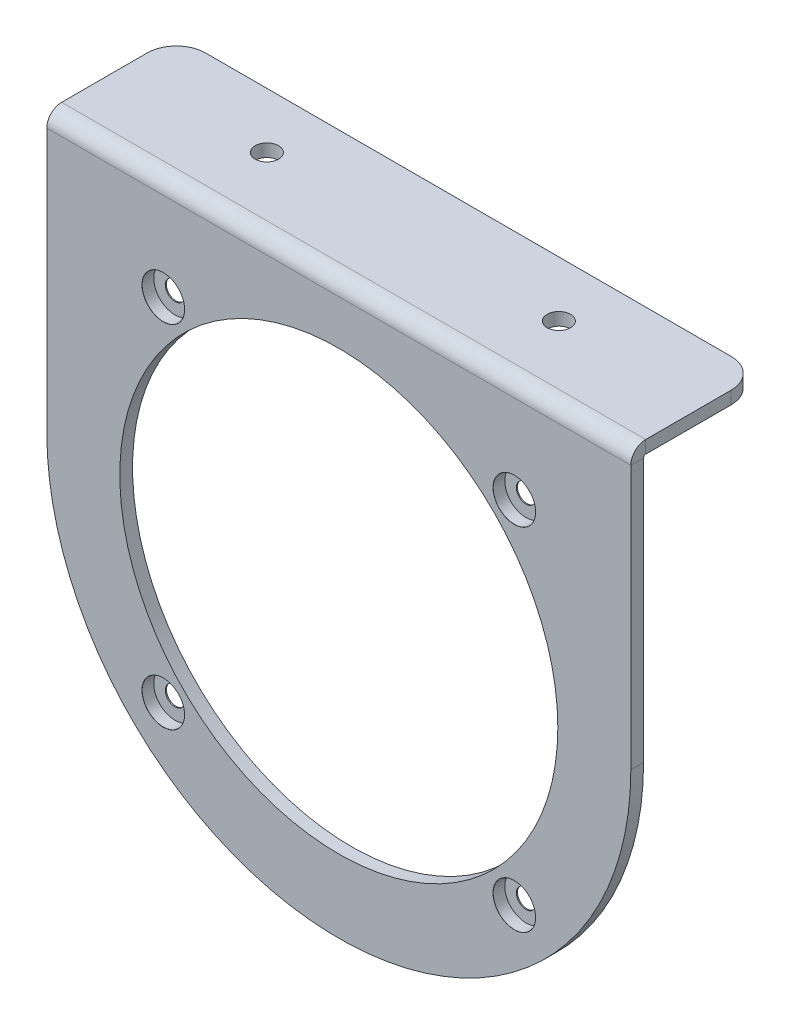
SolidWorks part; units mm, degrees
note: '?' marks a value the reader was unsure of. The reader was unsure of these and kept them because the rebuilt part matched: flange length of "Edge-Flange1"; thickness of "Edge-Flange1".
ref_plane "Front Plane" through (0, 0, 0) normal (0, 0, 1) x (1, 0, 0)
ref_plane "Top Plane" through (0, 0, 0) normal (0, 1, 0) x (1, 0, 0)
ref_plane "Right Plane" through (0, 0, 0) normal (1, 0, 0) x (0, 0, -1)
sketch "Sketch2" plane through (0, 0, 0) normal (0, 0, 1) x (1, 0, 0)
  line L0 (-100, 0) -> (-100, 95.4)
  line L1 (-100, 95.4) -> (100, 95.4)
  line L2 (100, 95.4) -> (100, 0)
  arc A0 (-100, 0) -> (100, 0) centre (0, 0) ccw
  dimension "D1" = 100
  dimension "D2" = 95.4
base flange "Base-Flange1" sketch "Sketch2" thickness 4.365 reverse thickness direction no parameters "D1"=0.7366
edge flange "Edge-Flange1" sketch "Sketch9" flange angle 90 flange length 40 flange position material inside bend radius 0.7366 thickness 4.365 relief rectangular parameters "D6"=10
sketch "Sketch9" plane through (0, 95.4, -4.365) normal (0, 1, 0) x (1, 0, 0)
  line L2 (-100, 0) -> (-100, 40)
  line L3 (-100, 40) -> (100, 40)
  line L4 (100, 40) -> (100, 0)
  line L11 (100, 0) -> (-100, 0) construction
  line L12 (100, 0) -> (-100, 0)
  dimension "D1" = 40
bend "EdgeBend1" bend radius 0.7366 bend angle 90 parameters "D5"=1
sketch "Sketch10" plane through (0, 0, 0) normal (0, 0, 1) x (1, 0, 0)
  circle A0 centre (0, 0) radius 75
  dimension "D1" = 150
extrude "Cut-Extrude1" cut sketch "Sketch10" against normal blind 10 normal cut yes
ref_axis "Axis1" through (0, 0, -4.365) along (0, 0, 1)?
fillet "Fillet1" radius 10 2 edges at (-100, 93.2175, -44.365) (100, 93.2175, -44.365)
sketch "Sketch12" plane through (0, 95.4, 0) normal (0, 1, 0) x (1, 0, 0)
  line L0 (0, 0) -> (0, 44.365) construction
  line L1 (90, 44.365) -> (-90, 44.365) construction
  line L3 (-50, 29.365) -> (-50, 44.365) construction
  circle A0 centre (-50, 25.365) radius 4
  circle A2 centre (50, 25.365) radius 4
  dimension "D1" = 8
  dimension "D2" = 50
  dimension "D3" = 15
extrude "Cut-Extrude3" cut sketch "Sketch12" against normal blind 10 normal cut yes
sketch "Sketch15" plane through (0, 0, 0) normal (0, 0, 1) x (1, 0, 0)
  line L0 (0, 0) -> (0, 85) construction
  line L2 (0, 0) -> (-85, 0) construction
  line L3 (0, 0) -> (-60.1041, 60.1041) construction
  circle A0 centre (0, 0) radius 85 construction
  point P22 (-60.1041, 60.1041)
  dimension "D2" = 85
hole_wizard "CBORE for M6 Hex Head Screw1" positions "Sketch15" profile "Sketch14" counterbore size "M6" standard "ISO" end condition through all
sketch "Sketch14" plane through (-60.1041, 60.1041, 0) normal (1, 0, 0) x (0, -1, 0)
  line L0 (0, 0) -> (0, 44.365)
  line L1 (0, 44.365) -> (3.3, 44.365)
  line L3 (3.3, 44.365) -> (3.3, 4)
  line L4 (7.2735, 4) -> (3.3, 4)
  line L5 (7.2735, 4) -> (7.2735, 0.025)
  line L6 (7.2735, 0.025) -> (7.2985, 0)
  line L7 (7.2985, 0) -> (0, 0)
  line L8 (-7.2735, 0.025) -> (-7.2985, 0) construction
  line L11 (0, -6.35) -> (0, 107.95) construction
  dimension "Thru Hole Dia." = 6.6
  dimension "Thru Hole Depth" = 44.365
  dimension "C'Bore Dia." = 14.547
  dimension "C'Bore Depth" = 4
  dimension "Near C'Sink Dia." = 14.597
  dimension "Near C'Sink Angle" = 90
pattern_circular "CirPattern1" count 4 over 360 about axis through (0, 0, 0) along (0, 0, 1) of "CBORE for M6 Hex Head Screw1"
sketch "Bend-Lines1" [suppressed] plane through (0, 0, 0) normal (0, 1, 0) x (1, 0, 0)
sketch "Bounding-Box1" [suppressed] plane through (0, 0, 0) normal (0, 1, 0) x (1, 0, 0)
sheet metal parameters "Sheet-Metal1" thickness 4.365 parameters "D1"=0.7366
flat pattern "Flat-Pattern1" [suppressed]
sketch "Bend-Lines2" plane through (0, 0, 0) normal (0, 1, 0) x (1, 0, 0)
sketch3d "Bounding-Box2" [suppressed]
  line L0 (-200, -200, 0) -> (200, -200, 0) construction
  line L1 (-200, 200, 0) -> (200, 200, 0) construction
  line L2 (-200, -200, 0) -> (-200, 200, 0) construction
  line L3 (200, -200, 0) -> (200, 200, 0) construction
sheet metal parameters "Sheet-Metal2" thickness 4.365 parameters "D1"=0.7366, "D7"=2
flat pattern "Flat-Pattern1"
sketch "Bend-Lines2" plane through (0, 0, 0) normal (0, 0, 1) x (1, 0, 0)
  line L0 (200, 197.1911) -> (-200, 197.1911) construction
  line L1 (200, 197.1911) -> (-200, 197.1911) construction
sketch3d "Bounding-Box2" [suppressed]
  line L0 (200, 298.7471, 0) -> (200, -200, 0) construction
  line L1 (-200, 298.7471, 0) -> (-200, -200, 0) construction
  line L2 (200, 298.7471, 0) -> (-200, 298.7471, 0) construction
  line L3 (200, -200, 0) -> (-200, -200, 0) construction
bend of the flat pattern "Flatten-<EdgeBend1>1"
sheet metal parameters "Sheet-Metal3" thickness 4.365 parameters "D1"=0.7366, "D7"=2
flat pattern "Flat-Pattern1"
sketch "Bend-Lines2" plane through (0, 0, 0) normal (0, 0, 1) x (1, 0, 0)
  line L0 (100, 147.1911) -> (-100, 147.1911) construction
  line L1 (100, 147.1911) -> (-100, 147.1911) construction
sketch3d "Bounding-Box2" [suppressed]
  line L0 (100, 248.7471, 0) -> (100, -100, 0) construction
  line L1 (-100, 248.7471, 0) -> (-100, -100, 0) construction
  line L2 (100, 248.7471, 0) -> (-100, 248.7471, 0) construction
  line L3 (100, -100, 0) -> (-100, -100, 0) construction
bend of the flat pattern "Flatten-<EdgeBend1>1"
sheet metal parameters "Sheet-Metal6" thickness 4.365 parameters "D1"=0.7366, "D7"=2
flat pattern "Flat-Pattern1"
sketch "Bend-Lines2" plane through (0, 0, 0) normal (0, 0, 1) x (1, 0, 0)
  line L0 (100, 147.1911) -> (-100, 147.1911) construction
  line L1 (100, 147.1911) -> (-100, 147.1911) construction
sketch3d "Bounding-Box2" [suppressed]
  line L0 (100, -100, 0) -> (100, 248.7471, 0) construction
  line L1 (-100, -100, 0) -> (-100, 248.7471, 0) construction
  line L2 (100, -100, 0) -> (-100, -100, 0) construction
  line L3 (100, 248.7471, 0) -> (-100, 248.7471, 0) construction
bend of the flat pattern "Flatten-<EdgeBend1>1"
sheet metal parameters "Sheet-Metal7" thickness 4.365 parameters "D1"=0.7366, "D7"=2
flat pattern "Flat-Pattern1"
sketch "Bend-Lines2" plane through (0, 0, 0) normal (0, 0, 1) x (1, 0, 0)
  line L0 (100, 147.1911) -> (-100, 147.1911) construction
  line L1 (100, 147.1911) -> (-100, 147.1911) construction
sketch3d "Bounding-Box2" [suppressed]
  line L0 (100, -100, 0) -> (100, 248.7471, 0) construction
  line L1 (-100, -100, 0) -> (-100, 248.7471, 0) construction
  line L2 (100, -100, 0) -> (-100, -100, 0) construction
  line L3 (100, 248.7471, 0) -> (-100, 248.7471, 0) construction
bend of the flat pattern "Flatten-<EdgeBend1>1"
sheet metal parameters "Sheet-Metal8" thickness 4.365 parameters "D1"=0.7366, "D7"=2
flat pattern "Flat-Pattern1"
sketch "Bend-Lines2" plane through (0, 0, 0) normal (0, 0, 1) x (1, 0, 0)
  line L0 (100, 92.5911) -> (-100, 92.5911) construction
  line L1 (100, 92.5911) -> (-100, 92.5911) construction
sketch3d "Bounding-Box2" [suppressed]
  line L0 (100, 134.1471, 0) -> (100, -100, 0) construction
  line L1 (-100, 134.1471, 0) -> (-100, -100, 0) construction
  line L2 (100, 134.1471, 0) -> (-100, 134.1471, 0) construction
  line L3 (100, -100, 0) -> (-100, -100, 0) construction
bend of the flat pattern "Flatten-<EdgeBend1>1"
